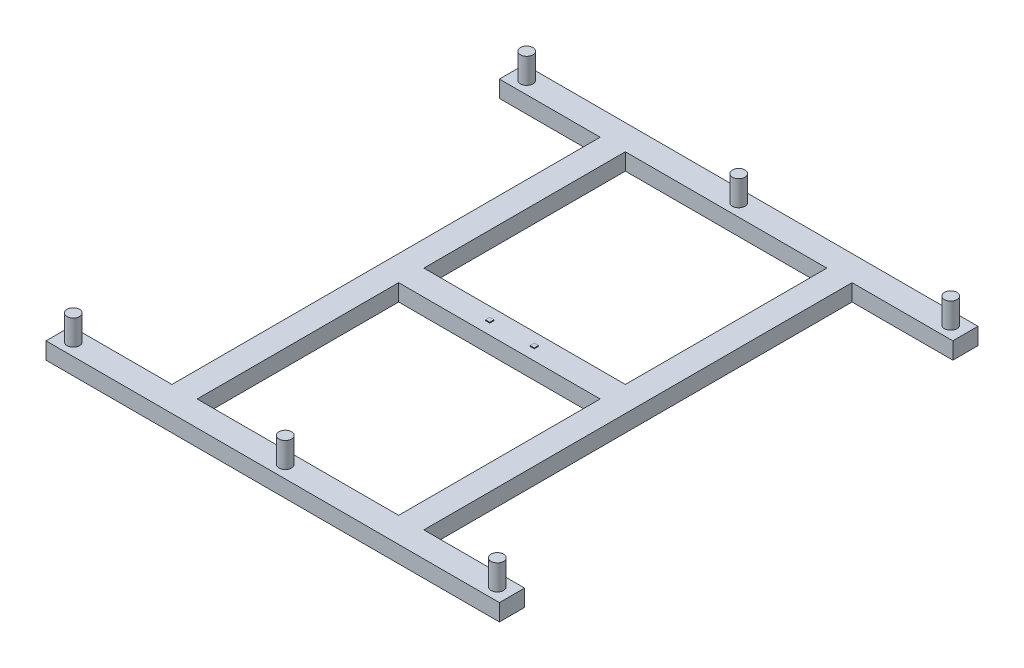
SolidWorks part; units mm, degrees
ref_plane "Front Plane" through (0, 0, 0) normal (0, 0, 1) x (1, 0, 0)
ref_plane "Top Plane" through (0, 0, 0) normal (0, 1, 0) x (1, 0, 0)
ref_plane "Right Plane" through (0, 0, 0) normal (1, 0, 0) x (0, 0, -1)
sketch "Sketch1" plane through (0, 0, 0) normal (0, 1, 0) x (1, 0, 0)
  line L0 (403.5942, 131.7666) -> (708.2609, 131.7666) construction
  line L1 (-150, 285) -> (150, 285)
  line L2 (-150, 285) -> (-150, -285)
  line L3 (-150, -285) -> (150, -285)
  line L4 (150, 285) -> (150, -285)
  line L5 (-120, 255) -> (120, 255)
  line L6 (-120, 255) -> (-120, 15)
  line L7 (-120, 15) -> (120, 15)
  line L8 (120, 255) -> (120, 15)
  line L9 (-120, -15) -> (120, -15)
  line L10 (-120, -15) -> (-120, -255)
  line L11 (-120, -255) -> (120, -255)
  line L12 (120, -15) -> (120, -255)
  line L14 (150, 285) -> (270, 285)
  line L16 (150, 255) -> (270, 255)
  line L17 (270, 285) -> (270, 255)
  line L18 (-150, 285) -> (-270, 285)
  line L20 (-150, 255) -> (-270, 255)
  line L21 (-270, 285) -> (-270, 255)
  line L22 (150, -285) -> (270, -285)
  line L24 (150, -255) -> (270, -255)
  line L25 (270, -285) -> (270, -255)
  line L26 (-150, -285) -> (-270, -285)
  line L28 (-150, -255) -> (-270, -255)
  line L29 (-270, -285) -> (-270, -255)
  dimension "D1" = 150
  dimension "D2" = 300
  dimension "D3" = 285
  dimension "D4" = 570
  dimension "D5" = 30
  dimension "D6" = 30
  dimension "D7" = 30
  dimension "D8" = 30
  dimension "D9" = 30
  dimension "D10" = 30
  dimension "D11" = 30
  dimension "D12" = 15
  dimension "D13" = 120
  dimension "D14" = 120
  dimension "D15" = 120
  dimension "D16" = 120
extrude "Boss-Extrude1" add sketch "Sketch1" along normal blind 20 contours L4 L1 L2 L3 L5 L8 L7 L6 L9 L12 L11 L10 region at (0, 0, 0)
extrude "Boss-Extrude2" add sketch "Sketch1<3>" along normal blind 20 contours L17 L14 L4 L16 | L18 L21 L20 L2 | L29 L26 L2 L28 | L22 L25 L24 L4 region at (-210, 0, -270) region at (210, 0, -270) region at (-210, 0, 270) region at (210, 0, 270)
sketch "Sketch1<3>" plane through (0, 0, 0) normal (0, 1, 0) x (1, 0, 0) same geometry as "Sketch1"
sketch "Sketch2" plane through (0, 20, 0) normal (0, 1, 0) x (1, 0, 0)
  line L0 (-270, 270) -> (270, 270) construction
  line L1 (-270, 285) -> (-270, 255) construction
  line L2 (270, 285) -> (270, 255) construction
  line L3 (-270, -270) -> (270, -270) construction
  line L4 (-270, -285) -> (-270, -255) construction
  line L5 (270, -285) -> (270, -255) construction
  circle A0 centre (0, 270) radius 7.5
  circle A1 centre (252.5, 270) radius 17.5
  circle A2 centre (252.5, 270) radius 7.5
  circle A3 centre (-252.5, 270) radius 17.5
  circle A4 centre (-252.5, 270) radius 7.5
  circle A5 centre (252.5, -270) radius 17.5
  circle A6 centre (-252.5, -270) radius 17.5
  circle A7 centre (-252.5, -270) radius 7.5
  circle A8 centre (252.5, -270) radius 7.5
  circle A9 centre (0, -270) radius 7.5
  dimension "D1" = 35
  dimension "D2" = 35
  dimension "D3" = 15
  dimension "D4" = 15
  dimension "D5" = 15
  dimension "D6" = 35
  dimension "D7" = 35
  dimension "D8" = 15
  dimension "D9" = 15
  dimension "D10" = 15
extrude "Boss-Extrude3" add sketch "Sketch2" along normal blind 30 contours A4 | A0 | A2 | A7 | A9 | A8
sketch "Sketch3" plane through (0, 20, 0) normal (0, 1, 0) x (1, 0, 0)
  line L0 (0, -270) -> (-272.8224, -270) construction
  line L1 (-120, -153.4186) -> (-120, -326.227) construction
  line L2 (-120, -15) -> (-120, -255) construction
  line L3 (120, -159.0783) -> (120, -340.1875) construction
  line L4 (120, -15) -> (120, -255) construction
  line L5 (-120, 173.3887) -> (-120, 347.4318) construction
  line L6 (-120, 255) -> (-120, 15) construction
  line L7 (120, 160.4434) -> (120, 349.5893) construction
  line L8 (120, 255) -> (120, 15) construction
  line L9 (0, 270) -> (155.8882, 270) construction
  line L10 (-120, 270) -> (0, 270) construction
sketch "Sketch4" plane through (0, 20, 0) normal (0, 1, 0) x (1, 0, 0)
  line L0 (-120, 15) -> (-120, -15) construction
  line L1 (-120, 0) -> (160.8557, 0) construction
  line L2 (120, 15) -> (120, -15) construction
  line L4 (-29, 2.5) -> (-24, 2.5)
  line L5 (-29, 2.5) -> (-29, -2.5)
  line L6 (-29, -2.5) -> (-24, -2.5)
  line L7 (-24, 2.5) -> (-24, -2.5)
  line L8 (24, 2.5) -> (29, 2.5)
  line L9 (24, 2.5) -> (24, -2.5)
  line L10 (24, -2.5) -> (29, -2.5)
  line L11 (29, 2.5) -> (29, -2.5)
  dimension "D1" = 24
  dimension "D2" = 24
  dimension "D3" = 5
  dimension "D4" = 5
  dimension "D5" = 5
  dimension "D6" = 5
  dimension "D7" = 2.5
  dimension "D8" = 2.5
extrude "Boss-Extrude4" add sketch "Sketch4" along normal blind 1
